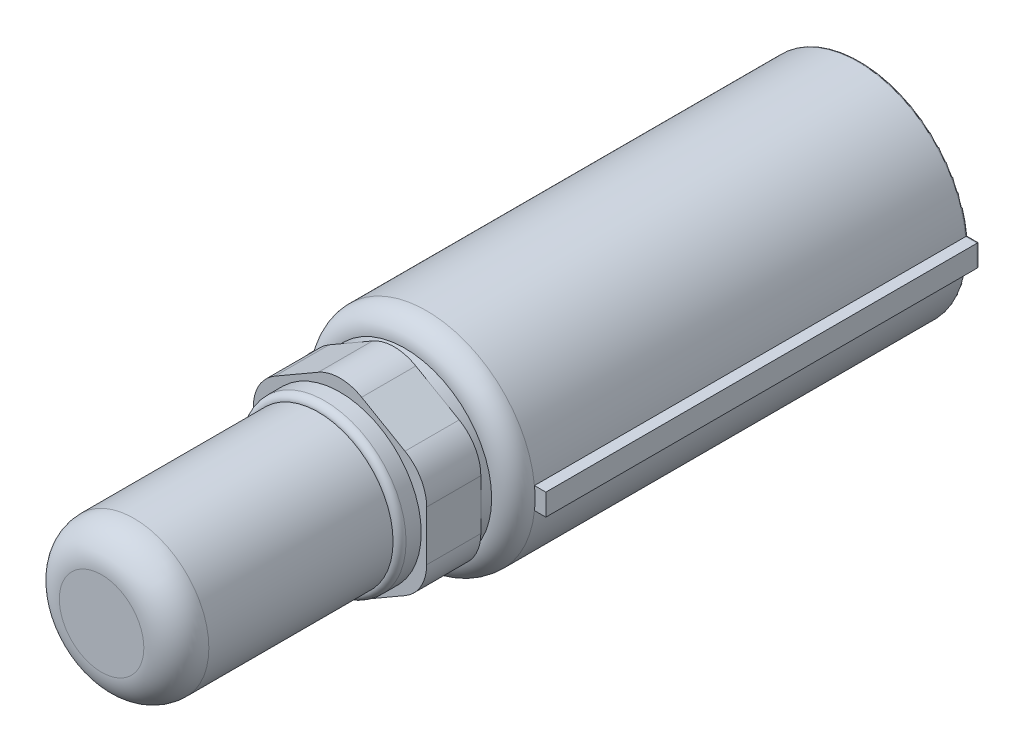
SolidWorks part; units mm, degrees
ref_plane "Front Plane" through (0, 0, 0) normal (0, 0, 1) x (1, 0, 0)
ref_plane "Top Plane" through (0, 0, 0) normal (0, 1, 0) x (1, 0, 0)
ref_plane "Right Plane" through (0, 0, 0) normal (1, 0, 0) x (0, 0, -1)
sketch "Sketch1" plane through (0, 0, 0) normal (0, 0, 1) x (1, 0, 0)
  circle A0 centre (0, 0) radius 12.7
  dimension "D1" = 25.4
extrude "Boss-Extrude1" add sketch "Sketch1" against normal blind 50.8 and the other way blind 2.54
fillet "Fillet1" radius 2.54 1 edges at (12.7, 0, 2.54)
sketch "Sketch2" plane through (0, 0, 2.54) normal (0, 0, 1) x (1, 0, 0)
  circle A0 centre (0, 0) radius 10.16
  dimension "D1" = 20.32
extrude "Boss-Extrude2" add sketch "Sketch2" along normal blind 1.27
sketch "Sketch3" plane through (0, 0, 3.81) normal (0, 0, 1) x (1, 0, 0)
  line L1 (10.16, -5.8659) -> (10.16, 5.8659)
  line L2 (10.16, 5.8659) -> (0, 11.7318)
  line L3 (0, 11.7318) -> (-10.16, 5.8659)
  line L4 (-10.16, 5.8659) -> (-10.16, -5.8659)
  line L5 (-10.16, -5.8659) -> (0, -11.7318)
  line L6 (0, -11.7318) -> (10.16, -5.8659)
  circle A0 centre (0, 0) radius 10.16 construction
  circle A1 centre (0, 0) radius 10.16 construction
extrude "Boss-Extrude3" add sketch "Sketch3" along normal blind 6.35
fillet "Fillet2" radius 5.08 6 edges at (-10.16, 5.8659, 6.985) (-10.16, -5.8659, 6.985) (0, -11.7318, 6.985) (10.16, -5.8659, 6.985) (0, 11.7318, 6.985) (10.16, 5.8659, 6.985)
sketch "Sketch4" plane through (0, 0, 10.16) normal (0, 0, 1) x (1, 0, 0)
  circle A0 centre (0, 0) radius 9.525
  dimension "D1" = 19.05
extrude "Boss-Extrude4" add sketch "Sketch4" along normal blind 2.54
fillet "Fillet3" radius 0.762 1 edges at (9.525, 0, 12.7)
sketch "Sketch5" plane through (0, 0, 12.7) normal (0, 0, 1) x (1, 0, 0)
  circle A0 centre (0, 0) radius 8.763
  circle A1 centre (0, 0) radius 8.763 construction
extrude "Boss-Extrude5" add sketch "Sketch5" along normal blind 25.4
fillet "Fillet4" radius 3.81 1 edges at (8.763, 0, 38.1)
sketch "Sketch6" plane through (0, 0, -50.8) normal (0, 0, -1) x (-1, 0, 0)
  line L1 (-13.97, -1.27) -> (13.97, -1.27)
  line L2 (-13.97, -1.27) -> (-13.97, 1.27)
  line L3 (-13.97, 1.27) -> (13.97, 1.27)
  line L4 (13.97, -1.27) -> (13.97, 1.27)
  line L5 (-13.97, -1.27) -> (13.97, 1.27) construction
  line L6 (-13.97, 1.27) -> (13.97, -1.27) construction
  point P0 (0, 0)
  dimension "D1" = 27.94
  dimension "D2" = 2.54
extrude "Boss-Extrude6" add sketch "Sketch6" against normal blind 50.8
fillet "Fillet5" radius 0.254 8 edges at (-13.3032, 1.27, -50.8) (-13.97, 0, -50.8) (-13.3032, -1.27, -50.8) (0, -12.7, -50.8) (13.3032, -1.27, -50.8) (13.97, 0, -50.8) (13.3032, 1.27, -50.8) (0, 12.7, -50.8)
